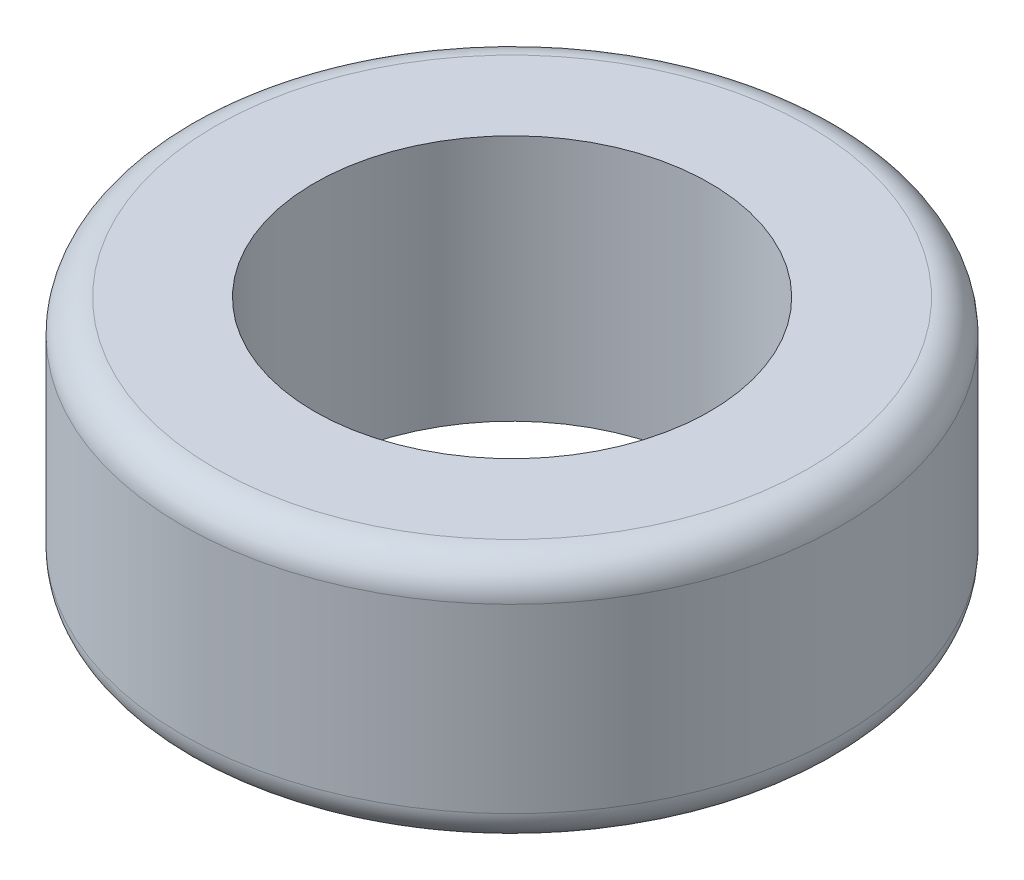
SolidWorks part; units mm, degrees
ref_plane "Front Plane" through (0, 0, 0) normal (0, 0, 1) x (1, 0, 0)
ref_plane "Top Plane" through (0, 0, 0) normal (0, 1, 0) x (1, 0, 0)
ref_plane "Right Plane" through (0, 0, 0) normal (1, 0, 0) x (0, 0, -1)
ref_axis "X-Axis" through (88.99, 0, 0) along (-1, 0, 0)
ref_axis "Y-Axis" through (0, 0, -88.99) along (0, 0, 1)
ref_axis "Z-Axis" through (0, -55, 0) along (0, 1, 0)
sketch "Sketch1" plane through (0, 0, 0) normal (0, 1, 0) x (1, 0, 0)
  circle A0 centre (0, 0) radius 10
  circle A1 centre (0, 0) radius 6
  dimension "D1" = 12
  dimension "D2" = 4
extrude "Boss-Extrude1" add sketch "Sketch1" along normal blind 7.5
fillet "Fillet1" radius 1 2 edges at (0, 0, 10) (0, 7.5, 10)
